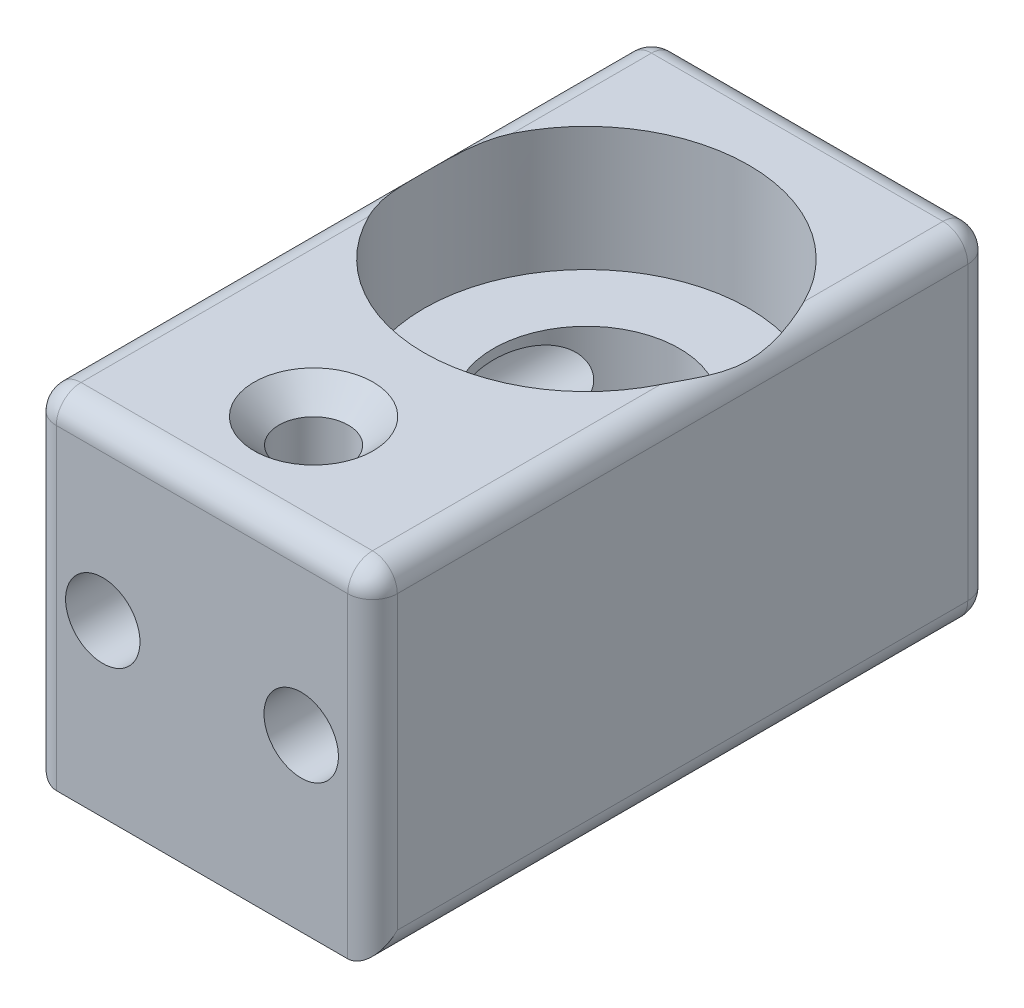
SolidWorks part; units mm, degrees
ref_plane "Front Plane" through (0, 0, 0) normal (0, 0, 1) x (1, 0, 0)
ref_plane "Top Plane" through (0, 0, 0) normal (0, 1, 0) x (1, 0, 0)
ref_plane "Right Plane" through (0, 0, 0) normal (1, 0, 0) x (0, 0, -1)
sketch "Sketch1" plane through (0, 0, 0) normal (0, 0, 1) x (1, 0, 0)
  line L1 (-6.875, -6.875) -> (6.875, -6.875)
  line L2 (-6.875, -6.875) -> (-6.875, 6.875)
  line L3 (-6.875, 6.875) -> (6.875, 6.875)
  line L4 (6.875, -6.875) -> (6.875, 6.875)
  line L5 (-6.875, -6.875) -> (6.875, 6.875) construction
  line L6 (-6.875, 6.875) -> (6.875, -6.875) construction
  point P0 (0, 0)
  dimension "D1" = 13.75
extrude "Boss-Extrude1" add sketch "Sketch1" along normal blind 25
ref_axis "Axis1" through (0, 0, -0.8) along (0, 0, 1)
sketch "Sketch3" plane through (0, 6.875, 0) normal (0, 1, 0) x (1, 0, 0)
  line L0 (0, -9.5) -> (0, 0) construction
  line L1 (6.875, 0) -> (-6.875, 0) construction
  circle A0 centre (0, -9.5) radius 6.5 construction
  circle A1 centre (0, -9.5) radius 3.75
  dimension "D1" = 13
  dimension "D3" = 7.5
  dimension "D2" = 3
extrude "Cut-Extrude2" cut sketch "Sketch3" against normal through all
sketch "Sketch4" plane through (0, 6.875, 0) normal (0, 1, 0) x (1, 0, 0)
  circle A0 centre (0, -9.5) radius 6.55
  dimension "D1" = 13.1
extrude "Cut-Extrude3" cut sketch "Sketch4" against normal blind 5
mirror "Mirror4" about plane through (0, 0, 0) normal (0, 1, 0) of "Cut-Extrude3"
sketch "Sketch8" plane through (0, 6.875, 0) normal (0, 1, 0) x (1, 0, 0)
  line L1 (0, 0) -> (0, -20.5) construction
  line L2 (6.875, 0) -> (-6.875, 0) construction
  circle A0 centre (0, -20.5) radius 1.4
  circle A1 centre (0, -9.5) radius 3.75 construction
  dimension "D1" = 11
  dimension "D2" = 2.8
extrude "Cut-Extrude6" cut sketch "Sketch8" against normal through all
sketch "Sketch9" plane through (0, 0, 0) normal (0, 0, -1) x (-1, 0, 0)
  line L0 (-4, 0) -> (0, 0) construction
  line L1 (-2, 1.1669) -> (-2, -1.0479) construction
  line L2 (0, 0.6668) -> (0, -0.643) construction
  circle A0 centre (-4, 0) radius 1.5
  dimension "D1" = 3
  dimension "D3" = 0.5
  dimension "D2" = 4
extrude "Cut-Extrude7" cut sketch "Sketch9" against normal through all
mirror "Mirror5" about plane through (0, 0, 0) normal (1, 0, 0) of "Cut-Extrude7"
chamfer "Chamfer1" distance 1 angle 45 2 edges at (0, -6.875, 21.9) (0, 6.875, 21.9)
fillet "Fillet2" radius 1 11 edges at (0, 6.875, 0) (-6.875, 0, 0) (0, -6.875, 0) (6.875, 0, 0) (6.875, 0, 25) (-6.875, 0, 25) (0, 6.875, 25) (6.875, -6.875, 12.5) (-6.875, -6.875, 12.5) (6.875, 6.875, 12.5) (-6.875, 6.875, 12.5)
